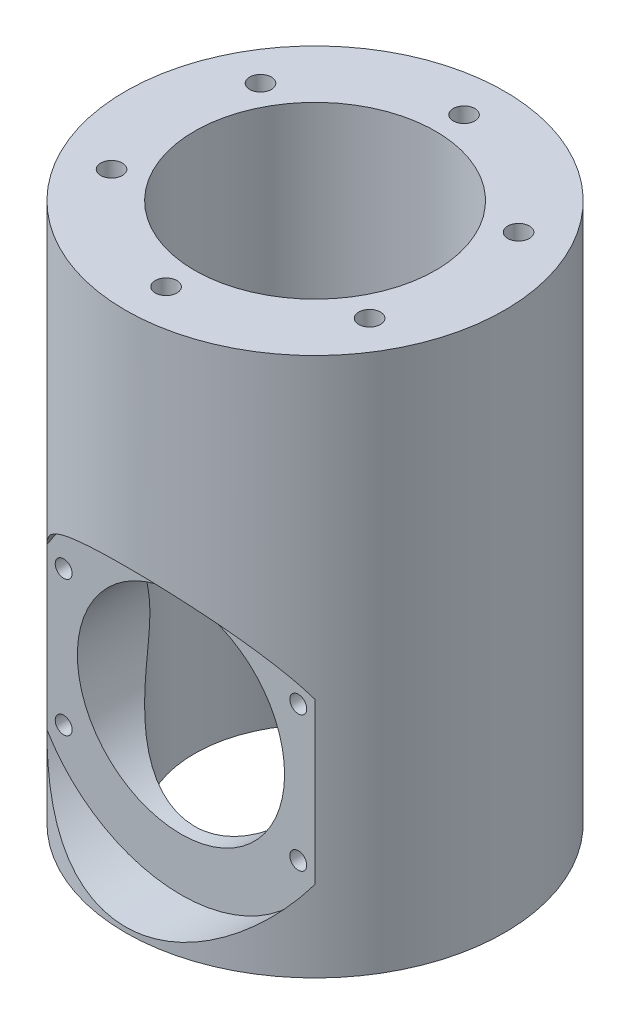
SolidWorks part; units mm, degrees
material "1060 Alloy"
ref_plane "Front Plane" through (0, 0, 0) normal (0, 0, 1) x (1, 0, 0)
ref_plane "Top Plane" through (0, 0, 0) normal (0, 1, 0) x (1, 0, 0)
ref_plane "Right Plane" through (0, 0, 0) normal (1, 0, 0) x (0, 0, -1)
sketch "Sketch1" plane through (0, 0, 0) normal (0, 0, 1) x (1, 0, 0)
  circle A0 centre (0, 0) radius 6.65
  circle A1 centre (0, 0) radius 7.15
  dimension "D1" = 13.3
  dimension "D2" = 14.3
extrude "Boss-Extrude1" add sketch "Sketch1" along normal blind 5
sketch "Sketch2" plane through (0, 0, 0) normal (0, 1, 0) x (1, 0, 0)
  circle A0 centre (0, 8.9) radius 8.9
  circle A1 centre (0, 8.9) radius 14
  dimension "D1" = 17.8
  dimension "D2" = 28
extrude "Boss-Extrude2" add sketch "Sketch2" along normal blind 27.9 and the other way blind 11.9
ref_plane "Plane4" through (0, -11.9, 0) normal (0, -1, 0) x (-1, 0, 0)
sketch "Sketch16" plane through (0, 0, 5) normal (0, 0, 1) x (1, 0, 0)
  circle A0 centre (0, 0) radius 6.65
  circle A1 centre (0, 0) radius 6.65 construction
  dimension "D1" = 0
extrude "Cut-Extrude3" cut sketch "Sketch16" against normal blind 17 and the other way blind 7
sketch "Sketch23" plane through (0, 0, 5) normal (0, 0, 1) x (1, 0, 0)
  circle A0 centre (0, 0) radius 7.05
  circle A1 centre (0, 0) radius 6.65
  circle A2 centre (0, 0) radius 6.65 construction
  dimension "D1" = 0
  dimension "D2" = 0.4
extrude "Cut-Extrude5" cut sketch "Sketch23" against normal blind 2
sketch "Sketch30" plane through (0, 0, 5) normal (0, 0, 1) x (1, 0, 0)
  circle A0 centre (0, 0) radius 7.65
  dimension "D1" = 15.3
extrude "Cut-Extrude8" cut sketch "Sketch30" against normal blind 11.28 and the other way blind 10
sketch "Sketch31" plane through (0, 27.9, 0) normal (0, 1, 0) x (1, 0, 0)
  circle A0 centre (0, 8.9) radius 11
  dimension "D1" = 22
hole_wizard "Tap Drill for M2 Tap1" positions "Sketch46" profile "Sketch47" hole size "M2" standard "ISO"
sketch "Sketch46" plane through (0, 27.9, 0) normal (0, 1, 0) x (1, 0, 0)
  circle A0 centre (0, 8.9) radius 8.9 construction
  point P0 (0, -2.1)
  dimension "D1" = 11
sketch "Sketch47" plane through (0, 27.9, 2.1) normal (1, 0, 0) x (0, 0, 1)
  line L0 (0, 0) -> (0, 4.4807)
  line L1 (0, 4.4807) -> (0.8, 4)
  line L2 (0.8, 4) -> (0.8, 0)
  line L5 (0.8, 0) -> (0, 0)
  line L10 (0, 4.4807) -> (-0.8, 4) construction
  line L11 (0, -6.35) -> (0, 107.95) construction
  dimension "Hole Dia." = 1.6
  dimension "Hole Depth" = 4
  dimension "Drill Angle" = 118
pattern_circular "CirPattern3" count 6 over 360 about axis through (0, -11.9, -8.9) along (0, 1, 0) of "Tap Drill for M2 Tap1" reverse direction yes
ref_plane "Plane6" through (0, 8, 0) normal (0, 1, 0) x (1, 0, 0)
mirror "Mirror1" about plane through (0, 8, 0) normal (0, 1, 0) of "CirPattern3"
sketch "Sketch39" plane through (0, -11.9, 0) normal (0, -1, 0) x (1, 0, 0)
  circle A0 centre (0, 2.1) radius 1.8168
extrude "Boss-Extrude3" add sketch "Sketch39" against normal up to surface (4.25 mm away) up to face at (0.3182, -7.6434, 2.2944)
sketch "Sketch38" plane through (0, 0, 0) normal (0, 0, 1) x (1, 0, 0)
  circle A0 centre (0, 0) radius 11.53
  dimension "D1" = 23.06
extrude "Cut-Extrude11" cut sketch "Sketch38" along normal blind 10 from offset 1 contours A0 region at (0, 0, 0)
hole_wizard "Tap Drill for M1.6 Tap1" positions "Sketch48" profile "Sketch49" hole size "M1.6" standard "ISO"
sketch "Sketch48" plane through (0, 0, 1) normal (0, 0, 1) x (1, 0, 0)
  line L0 (-14.573, 0) -> (17.3722, 0) construction
  line L2 (-8.6603, 5) -> (0, 0) construction
  point P0 (-8.6603, 5)
  dimension "D1" = 10
  dimension "D2" = 30
sketch "Sketch49" plane through (-8.6603, 5, 1) normal (1, 0, 0) x (0, -1, 0)
  line L0 (0, 0) -> (0, 5.3755)
  line L1 (0, 5.3755) -> (0.625, 5)
  line L2 (0.625, 5) -> (0.625, 0)
  line L5 (0.625, 0) -> (0, 0)
  line L10 (0, 5.3755) -> (-0.625, 5) construction
  line L11 (0, -6.35) -> (0, 107.95) construction
  dimension "Hole Dia." = 1.25
  dimension "Hole Depth" = 5
  dimension "Drill Angle" = 118
pattern_circular "CirPattern4" count 6 over 360 about axis through (0, 0, 15) along (0, 0, -1) skipping 2, 5 of "Tap Drill for M1.6 Tap1" reverse direction yes
